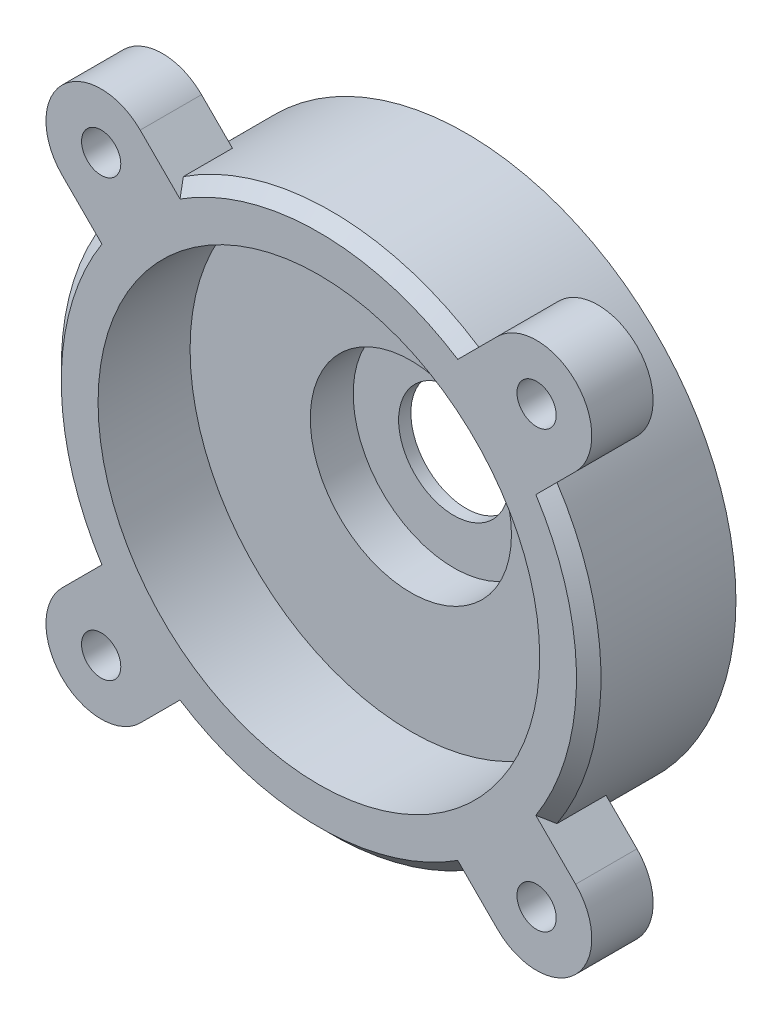
SolidWorks part; units mm, degrees
ref_plane "Front Plane" through (0, 0, 0) normal (0, 0, 1) x (1, 0, 0)
ref_plane "Top Plane" through (0, 0, 0) normal (0, 1, 0) x (1, 0, 0)
ref_plane "Right Plane" through (0, 0, 0) normal (1, 0, 0) x (0, 0, -1)
sketch "Sketch1" plane through (0, 0, 0) normal (0, 0, 1) x (1, 0, 0)
  circle A0 centre (0, 0) radius 22
  dimension "D1" = 44
extrude "Boss-Extrude1" add sketch "Sketch1" along normal mid plane 12
chamfer "Chamfer1" distance 1 angle 45 1 edges at (22, 0, 6)
sketch "Sketch8" plane through (0, 0, 6) normal (0, 0, 1) x (1, 0, 0)
  line L17 (20.9304, -14.5664) -> (17.6863, -11.3223)
  line L19 (14.5664, 20.9304) -> (11.3223, 17.6863)
  line L20 (20.9304, 14.5664) -> (17.6863, 11.3223)
  line L21 (17.6863, 11.3223) -> (11.3223, 17.6863)
  line L22 (14.5664, -20.9304) -> (11.3223, -17.6863)
  line L23 (11.3223, -17.6863) -> (17.6863, -11.3223)
  line L24 (-14.5664, -20.9304) -> (-11.3223, -17.6863)
  line L25 (-20.9304, -14.5664) -> (-17.6863, -11.3223)
  line L26 (-17.6863, -11.3223) -> (-11.3223, -17.6863)
  line L27 (-20.9304, 14.5664) -> (-17.6863, 11.3223)
  line L28 (-14.5664, 20.9304) -> (-11.3223, 17.6863)
  line L29 (-11.3223, 17.6863) -> (-17.6863, 11.3223)
  circle A2 centre (17.7484, 17.7484) radius 1.6
  circle A12 centre (0, 0) radius 21 construction
  arc A14 (14.5664, 20.9304) -> (20.9304, 14.5664) centre (17.7484, 17.7484) cw
  circle A15 centre (17.7484, -17.7484) radius 1.6
  arc A16 (20.9304, -14.5664) -> (14.5664, -20.9304) centre (17.7484, -17.7484) cw
  circle A17 centre (-17.7484, -17.7484) radius 1.6
  arc A18 (-14.5664, -20.9304) -> (-20.9304, -14.5664) centre (-17.7484, -17.7484) cw
  circle A19 centre (-17.7484, 17.7484) radius 1.6
  arc A20 (-20.9304, 14.5664) -> (-14.5664, 20.9304) centre (-17.7484, 17.7484) cw
  point P6 (17.7484, 17.7484)
  point P9 (0, 0)
  point P19 (17.7484, -17.7484)
  point P27 (-17.7484, -17.7484)
  point P31 (0, 0)
  point P36 (-17.7484, 17.7484)
  point P40 (0, 0)
  dimension "D1" = 4
extrude "Boss-Extrude2" add sketch "Sketch8" against normal blind 5
sketch "Sketch9" plane through (0, 0, 6) normal (0, 0, 1) x (1, 0, 0)
  circle A0 centre (0, 0) radius 18
extrude "Cut-Extrude1" cut sketch "Sketch9" against normal blind 7.5
sketch "Sketch10" plane through (0, 0, -1.5) normal (0, 0, 1) x (1, 0, 0)
  circle A0 centre (0, 0) radius 8.2
extrude "Cut-Extrude2" cut sketch "Sketch10" against normal blind 3.5
sketch "Sketch11" plane through (0, 0, -5) normal (0, 0, 1) x (1, 0, 0)
  circle A0 centre (0, 0) radius 4.5
extrude "Cut-Extrude3" cut sketch "Sketch11" against normal up to surface (1 mm away) up to face at (22, 0, -6)
